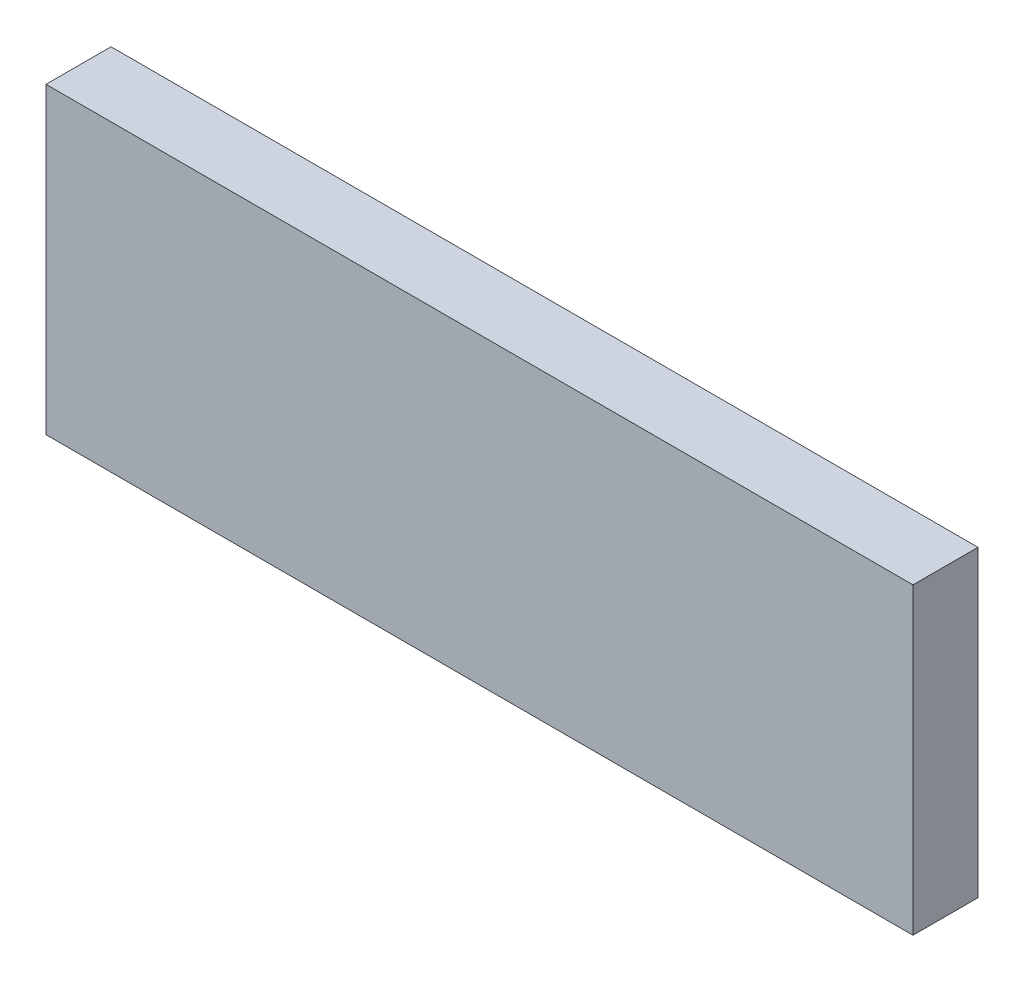
SolidWorks part; units mm, degrees
ref_plane "Alzado" through (0, 0, 0) normal (0, 0, 1) x (1, 0, 0)
ref_plane "Planta" through (0, 0, 0) normal (0, 1, 0) x (1, 0, 0)
ref_plane "Vista lateral" through (0, 0, 0) normal (1, 0, 0) x (0, 0, -1)
sketch "Croquis1" plane through (0, 0, 0) normal (0, 0, 1) x (1, 0, 0)
  line L1 (80, 28) -> (0, 28)
  line L2 (80, 28) -> (80, 0)
  line L3 (80, 0) -> (0, 0)
  line L4 (0, 28) -> (0, 0)
  dimension "D1" = 28
  dimension "D2" = 80
extrude "Saliente-Extruir1" add sketch "Croquis1" along normal blind 6
